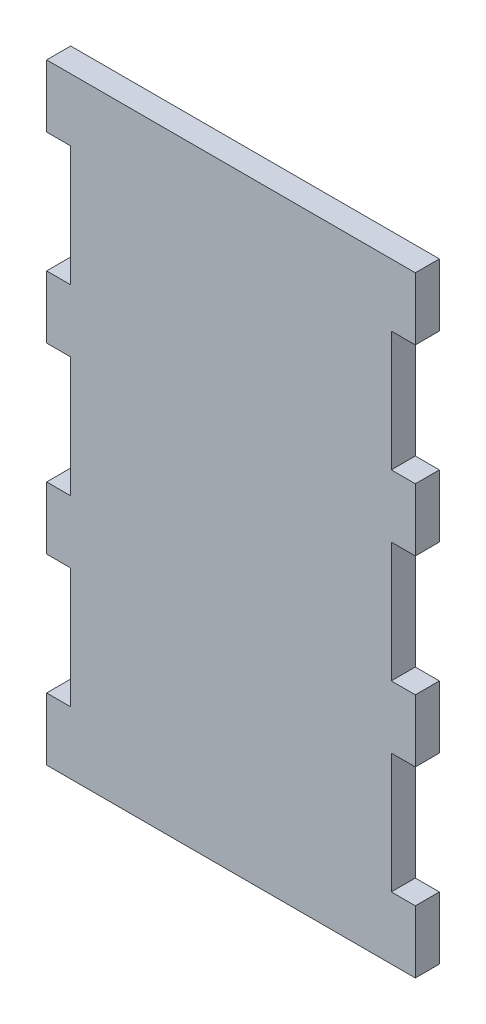
SolidWorks part; units mm, degrees
material "Oak"
ref_plane "Front Plane" through (0, 0, 0) normal (0, 0, 1) x (1, 0, 0)
ref_plane "Top Plane" through (0, 0, 0) normal (0, 1, 0) x (1, 0, 0)
ref_plane "Right Plane" through (0, 0, 0) normal (1, 0, 0) x (0, 0, -1)
sketch "Sketch1" plane through (0, 0, 0) normal (0, 0, 1) x (1, 0, 0)
  line L1 (-40.9935, 16.542) -> (5.0065, 16.542)
  line L2 (-40.9935, 16.542) -> (-40.9935, -59.658)
  line L3 (-40.9935, -59.658) -> (5.0065, -59.658)
  line L4 (5.0065, 16.542) -> (5.0065, -59.658)
  dimension "D1" = 76.2
  dimension "D2" = 46
extrude "Boss-Extrude1" add sketch "Sketch1" along normal blind 3
sketch "Sketch2" plane through (0, 0, 3) normal (0, 0, 1) x (1, 0, 0)
  line L0 (-40.9935, 16.542) -> (-40.9935, -59.658) construction
  line L1 (-40.9935, 8.742) -> (-37.9935, 8.742)
  line L2 (-40.9935, 8.742) -> (-40.9935, -6.258)
  line L3 (-40.9935, -6.258) -> (-37.9935, -6.258)
  line L4 (-37.9935, 8.742) -> (-37.9935, -6.258)
  line L5 (5.0065, 16.542) -> (-40.9935, 16.542) construction
  line L6 (5.0065, -59.658) -> (5.0065, 16.542) construction
  line L7 (5.0065, 8.742) -> (2.0065, 8.742)
  line L8 (5.0065, 8.742) -> (5.0065, -6.258)
  line L9 (5.0065, -6.258) -> (2.0065, -6.258)
  line L10 (2.0065, 8.742) -> (2.0065, -6.258)
  point P8 (-39.4935, 8.742)
  dimension "D1" = 3
  dimension "D2" = 7.8
  dimension "D3" = 15
  dimension "D4" = 3
  dimension "D5" = 7.8
  dimension "D6" = 15
extrude "Cut-Extrude1" cut sketch "Sketch2" against normal through all
pattern_linear "LPattern1" count 3 spacing 22.8 along (0, -1, 0) of "Cut-Extrude1"
